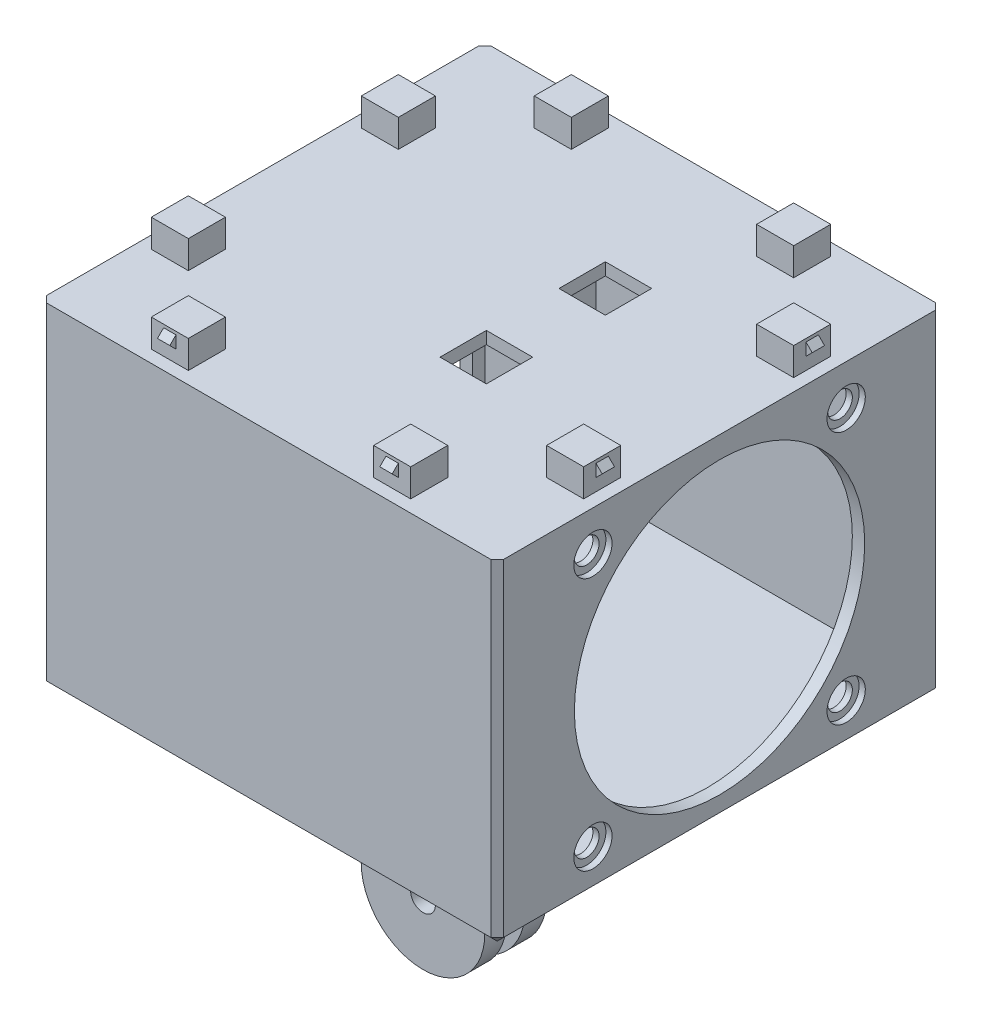
SolidWorks part; units mm, degrees
ref_plane "前视基准面" through (0, 0, 0) normal (0, 0, 1) x (1, 0, 0)
ref_plane "上视基准面" through (0, 0, 0) normal (0, 1, 0) x (1, 0, 0)
ref_plane "右视基准面" through (0, 0, 0) normal (1, 0, 0) x (0, 0, -1)
sketch "草图1" plane through (0, 0, 0) normal (0, 1, 0) x (1, 0, 0)
  line L1 (-65.7153, 32.1762) -> (8.2847, 32.1762)
  line L2 (-65.7153, 32.1762) -> (-65.7153, -39.8238)
  line L3 (-65.7153, -39.8238) -> (8.2847, -39.8238)
  line L4 (8.2847, 32.1762) -> (8.2847, -39.8238)
  dimension "D1" = 74
  dimension "D5" = 72
extrude "凸台-拉伸1" add sketch "草图1" along normal blind 54
sketch "草图2" plane through (0, 54, 0) normal (0, 1, 0) x (1, 0, 0)
  line L0 (8.2847, -39.8238) -> (8.2847, 32.1762) construction
  line L1 (6.2847, 30.1762) -> (-63.7153, 30.1762)
  line L2 (6.2847, 30.1762) -> (6.2847, -37.8238)
  line L3 (6.2847, -37.8238) -> (-63.7153, -37.8238)
  line L4 (-63.7153, 30.1762) -> (-63.7153, -37.8238)
  line L5 (-65.7153, -39.8238) -> (8.2847, -39.8238) construction
  line L6 (8.2847, 32.1762) -> (-65.7153, 32.1762) construction
  line L7 (-65.7153, 32.1762) -> (-65.7153, -39.8238) construction
  dimension "D1" = 2
  dimension "D2" = 2
  dimension "D3" = 2
  dimension "D4" = 2
extrude "切除-拉伸1" cut sketch "草图2" against normal blind 52
sketch "草图4" plane through (8.2847, 0, 0) normal (1, 0, 0) x (0, 0, -1)
  line L1 (32.1762, 54) -> (32.1762, 0) construction
  line L2 (-39.8238, 0) -> (32.1762, 0) construction
  circle A0 centre (-3.8238, 27) radius 23.5
  circle A1 centre (16.6762, 6.5) radius 2
  circle A2 centre (-24.3238, 47.5) radius 2
  circle A3 centre (-24.3238, 6.5) radius 2
  circle A4 centre (16.6762, 47.5) radius 2
  dimension "D1" = 47
  dimension "D2" = 20.5
  dimension "D8" = 4
  dimension "D3" = 20.5
  dimension "D4" = 20.5
  dimension "D5" = 20.5
  dimension "D6" = 36
  dimension "D7" = 27
extrude "切除-拉伸2" cut sketch "草图4" against normal blind 2
sketch "草图5" plane through (0, 0, 0) normal (0, -1, 0) x (1, 0, 0)
  line L0 (-65.7153, -32.1762) -> (-65.7153, 39.8238) construction
  line L1 (-63.7153, 37.8238) -> (-49.7153, 37.8238)
  line L2 (-63.7153, 37.8238) -> (-63.7153, -30.1762)
  line L3 (-63.7153, -30.1762) -> (-49.7153, -30.1762)
  line L4 (-49.7153, 37.8238) -> (-49.7153, -30.1762)
  line L5 (-65.7153, 39.8238) -> (8.2847, 39.8238) construction
  line L6 (8.2847, -32.1762) -> (-65.7153, -32.1762) construction
  dimension "D1" = 2
  dimension "D2" = 2
  dimension "D3" = 2
  dimension "D4" = 14
extrude "切除-拉伸3" cut sketch "草图5" against normal blind 2
sketch "草图6" plane through (0, 0, 37.8238) normal (0, 0, -1) x (-1, 0, 0)
  line L0 (63.7153, 54) -> (-6.2847, 54) construction
  line L1 (63.7153, 52) -> (54.7153, 52)
  line L2 (63.7153, 52) -> (63.7153, 54)
  line L3 (63.7153, 54) -> (54.7153, 54)
  line L4 (54.7153, 52) -> (54.7153, 54)
  line L9 (63.7153, 0) -> (63.7153, 54) construction
  dimension "D1" = 9
  dimension "D2" = 2
  dimension "D3" = 0
  dimension "D4" = 0
sketch "草图7" plane through (0, 0, -30.1762) normal (0, 0, 1) x (1, 0, 0)
  line L0 (-54.7153, 52) -> (-54.7153, 54) construction
  line L1 (-63.7153, 54) -> (-54.7153, 54)
  line L2 (-63.7153, 54) -> (-63.7153, 52)
  line L3 (-63.7153, 52) -> (-54.7153, 52)
  line L4 (-54.7153, 54) -> (-54.7153, 52)
  line L5 (-63.7153, 54) -> (-54.7153, 54) construction
  line L6 (6.2847, 54) -> (-63.7153, 54) construction
  line L7 (-63.7153, 0) -> (-63.7153, 54) construction
  point P12 (-63.7153, 53)
  dimension "D1" = 0
extrude "凸台-拉伸2" add sketch "草图6" along normal blind 5
extrude "凸台-拉伸3" add sketch "草图7" along normal blind 5
sketch "草图9" plane through (-65.7153, 0, 0) normal (-1, 0, 0) x (0, 0, 1)
  line L0 (39.8238, 54) -> (39.8238, 0) construction
  line L1 (35.8238, 50) -> (-28.1762, 50)
  line L2 (35.8238, 50) -> (35.8238, 4)
  line L3 (35.8238, 4) -> (-28.1762, 4)
  line L4 (-28.1762, 50) -> (-28.1762, 4)
  line L5 (-32.1762, 0) -> (39.8238, 0) construction
  line L6 (-32.1762, 54) -> (39.8238, 54) construction
  line L7 (-32.1762, 54) -> (-32.1762, 0) construction
  dimension "D1" = 4
  dimension "D2" = 4
  dimension "D3" = 4
  dimension "D4" = 4
extrude "切除-拉伸4" cut sketch "草图9" against normal up to next
sketch "草图10" plane through (0, 0, 37.8238) normal (0, 0, -1) x (-1, 0, 0)
  line L0 (49.7153, 2) -> (-6.2847, 2) construction
  line L9 (49.7153, 10) -> (45.7153, 10)
  line L10 (49.7153, 10) -> (49.7153, 18)
  line L11 (49.7153, 18) -> (45.7153, 18)
  line L12 (45.7153, 10) -> (45.7153, 18)
  line L13 (49.7153, 25) -> (49.7153, 33)
  line L14 (49.7153, 25) -> (45.7153, 25)
  line L15 (45.7153, 25) -> (45.7153, 33)
  line L16 (49.7153, 33) -> (45.7153, 33)
  line L17 (49.7153, 40) -> (49.7153, 48)
  line L18 (49.7153, 40) -> (45.7153, 40)
  line L19 (45.7153, 40) -> (45.7153, 48)
  line L20 (49.7153, 48) -> (45.7153, 48)
  line L21 (49.7153, 2) -> (49.7153, 0) construction
  point P0 (47.7153, 10)
  dimension "D1" = 4
  dimension "D2" = 8
  dimension "D3" = 8
  dimension "D4" = 3
extrude "凸台-拉伸5" add sketch "草图10" along normal blind 5
sketch "草图11" plane through (0, 0, -30.1762) normal (0, 0, 1) x (1, 0, 0)
  line L0 (6.2847, 2) -> (-49.7153, 2) construction
  line L1 (-45.7153, 10) -> (-49.7153, 10)
  line L2 (-45.7153, 10) -> (-45.7153, 18)
  line L3 (-45.7153, 18) -> (-49.7153, 18)
  line L4 (-49.7153, 10) -> (-49.7153, 18)
  line L5 (-45.7153, 25) -> (-45.7153, 33)
  line L6 (-45.7153, 25) -> (-49.7153, 25)
  line L7 (-49.7153, 25) -> (-49.7153, 33)
  line L8 (-45.7153, 33) -> (-49.7153, 33)
  line L9 (-45.7153, 40) -> (-45.7153, 48)
  line L10 (-45.7153, 40) -> (-49.7153, 40)
  line L11 (-49.7153, 40) -> (-49.7153, 48)
  line L12 (-45.7153, 48) -> (-49.7153, 48)
  line L13 (-49.7153, 2) -> (-49.7153, 0) construction
  dimension "D1" = 4
  dimension "D2" = 8
  dimension "D3" = 8
  dimension "D4" = 3
extrude "凸台-拉伸6" add sketch "草图11" along normal blind 5
sketch "草图15" plane through (0, 54, 0) normal (0, 1, 0) x (1, 0, 0)
  line L0 (6.2847, -37.8238) -> (6.2847, 30.1762) construction
  line L1 (-63.7153, 30.1762) -> (6.2847, 30.1762)
  line L2 (-63.7153, 30.1762) -> (-63.7153, -37.8238)
  line L3 (-63.7153, -37.8238) -> (6.2847, -37.8238)
  line L4 (6.2847, 30.1762) -> (6.2847, -37.8238)
  line L5 (-63.7153, 25.1762) -> (-63.7153, -32.8238) construction
extrude "凸台-拉伸7" add sketch "草图15" against normal blind 2
sketch "草图16" plane through (0, 54, 0) normal (0, 1, 0) x (1, 0, 0)
  line L0 (-43.7153, -31.8238) -> (-49.7153, -31.8238)
  line L1 (-57.7153, 16.1762) -> (-63.7153, 16.1762)
  line L2 (-57.7153, 16.1762) -> (-57.7153, 10.1762)
  line L3 (-57.7153, 10.1762) -> (-63.7153, 10.1762)
  line L4 (-63.7153, 16.1762) -> (-63.7153, 10.1762)
  line L5 (-43.7153, -31.8238) -> (-43.7153, -37.8238)
  line L6 (-43.7153, -37.8238) -> (-49.7153, -37.8238)
  line L7 (-49.7153, -31.8238) -> (-49.7153, -37.8238)
  line L8 (-7.7153, -31.8238) -> (-13.7153, -31.8238)
  line L9 (-7.7153, -31.8238) -> (-7.7153, -37.8238)
  line L10 (-7.7153, -37.8238) -> (-13.7153, -37.8238)
  line L11 (-13.7153, -31.8238) -> (-13.7153, -37.8238)
  line L12 (-43.7153, 30.1762) -> (-49.7153, 30.1762)
  line L13 (-43.7153, 30.1762) -> (-43.7153, 24.1762)
  line L14 (-43.7153, 24.1762) -> (-49.7153, 24.1762)
  line L15 (-49.7153, 30.1762) -> (-49.7153, 24.1762)
  line L16 (-7.7153, 30.1762) -> (-13.7153, 30.1762)
  line L17 (-7.7153, 30.1762) -> (-7.7153, 24.1762)
  line L18 (-7.7153, 24.1762) -> (-13.7153, 24.1762)
  line L19 (-13.7153, 30.1762) -> (-13.7153, 24.1762)
  line L20 (6.2847, 16.1762) -> (0.2847, 16.1762)
  line L21 (6.2847, 16.1762) -> (6.2847, 10.1762)
  line L22 (6.2847, 10.1762) -> (0.2847, 10.1762)
  line L23 (0.2847, 16.1762) -> (0.2847, 10.1762)
  line L24 (6.2847, -17.8238) -> (0.2847, -17.8238)
  line L25 (6.2847, -17.8238) -> (6.2847, -23.8238)
  line L26 (6.2847, -23.8238) -> (0.2847, -23.8238)
  line L27 (0.2847, -17.8238) -> (0.2847, -23.8238)
  line L32 (-57.7153, -17.8238) -> (-63.7153, -17.8238)
  line L33 (-57.7153, -17.8238) -> (-57.7153, -23.8238)
  line L34 (-57.7153, -23.8238) -> (-63.7153, -23.8238)
  line L35 (-63.7153, -17.8238) -> (-63.7153, -23.8238)
  line L36 (8.2847, 32.1762) -> (-65.7153, 32.1762) construction
  line L37 (-65.7153, -39.8238) -> (8.2847, -39.8238) construction
  line L38 (-65.7153, 32.1762) -> (-65.7153, -39.8238) construction
  line L39 (8.2847, -39.8238) -> (8.2847, 32.1762) construction
  point P42 (-10.7153, 30.1762)
  dimension "D1" = 16
  dimension "D2" = 16
  dimension "D3" = 16
  dimension "D4" = 16
  dimension "D5" = 16
  dimension "D6" = 16
  dimension "D7" = 16
  dimension "D8" = 16
  dimension "D9" = 6
  dimension "D10" = 2
  dimension "D11" = 2
  dimension "D12" = 2
  dimension "D13" = 2
extrude "凸台-拉伸8" add sketch "草图16" along normal blind 4.5
sketch "草图17" plane through (-63.7153, 0, 0) normal (-1, 0, 0) x (0, 0, 1)
  line L1 (-14.1762, 58) -> (-12.1762, 58)
  line L2 (-14.1762, 58) -> (-14.1762, 56)
  line L3 (-14.1762, 56) -> (-12.1762, 56)
  line L4 (-12.1762, 58) -> (-12.1762, 56)
  line L5 (19.8238, 58) -> (21.8238, 58)
  line L6 (19.8238, 58) -> (19.8238, 56)
  line L7 (19.8238, 56) -> (21.8238, 56)
  line L8 (21.8238, 58) -> (21.8238, 56)
  line L9 (17.8238, 54) -> (23.8238, 54) construction
  line L10 (23.8238, 58.5) -> (23.8238, 54) construction
  line L11 (-10.1762, 58.5) -> (-10.1762, 54) construction
  dimension "D1" = 2
  dimension "D2" = 2
  dimension "D3" = 2
  dimension "D4" = 2
extrude "凸台-拉伸9" add sketch "草图17" along normal blind 1
sketch "草图18" plane through (0, 0, 37.8238) normal (0, 0, 1) x (1, 0, 0)
  line L0 (-13.7153, 54) -> (-7.7153, 54) construction
  line L1 (-9.7153, 56) -> (-11.7153, 56)
  line L2 (-9.7153, 56) -> (-9.7153, 58)
  line L3 (-9.7153, 58) -> (-11.7153, 58)
  line L4 (-11.7153, 56) -> (-11.7153, 58)
  line L5 (-45.7153, 56) -> (-47.7153, 56)
  line L6 (-45.7153, 56) -> (-45.7153, 58)
  line L7 (-45.7153, 58) -> (-47.7153, 58)
  line L8 (-47.7153, 56) -> (-47.7153, 58)
  line L9 (-7.7153, 58.5) -> (-7.7153, 54) construction
  line L10 (-43.7153, 58.5) -> (-43.7153, 54) construction
  point P11 (-9.7153, 57)
  dimension "D1" = 2
  dimension "D2" = 2
  dimension "D3" = 2
  dimension "D4" = 2
extrude "凸台-拉伸10" add sketch "草图18" along normal blind 1
sketch "草图19" plane through (6.2847, 0, 0) normal (1, 0, 0) x (0, 0, -1)
  line L0 (10.1762, 54) -> (16.1762, 54) construction
  line L1 (14.1762, 56) -> (12.1762, 56)
  line L2 (14.1762, 56) -> (14.1762, 58)
  line L3 (14.1762, 58) -> (12.1762, 58)
  line L4 (12.1762, 56) -> (12.1762, 58)
  line L5 (-19.8238, 56) -> (-21.8238, 56)
  line L6 (-19.8238, 56) -> (-19.8238, 58)
  line L7 (-19.8238, 58) -> (-21.8238, 58)
  line L8 (-21.8238, 56) -> (-21.8238, 58)
  line L9 (16.1762, 58.5) -> (16.1762, 54) construction
  line L10 (-17.8238, 58.5) -> (-17.8238, 54) construction
  dimension "D1" = 2
  dimension "D2" = 2
  dimension "D3" = 2
  dimension "D4" = 2
extrude "凸台-拉伸11" add sketch "草图19" along normal blind 1
sketch "草图20" plane through (0, 0, -30.1762) normal (0, 0, -1) x (-1, 0, 0)
  line L1 (47.7153, 56) -> (45.7153, 56)
  line L2 (47.7153, 56) -> (47.7153, 58)
  line L3 (47.7153, 58) -> (45.7153, 58)
  line L4 (45.7153, 56) -> (45.7153, 58)
  line L5 (11.7153, 56) -> (9.7153, 56)
  line L6 (11.7153, 56) -> (11.7153, 58)
  line L7 (11.7153, 58) -> (9.7153, 58)
  line L8 (9.7153, 56) -> (9.7153, 58)
  line L9 (43.7153, 54) -> (49.7153, 54) construction
  line L10 (49.7153, 58.5) -> (49.7153, 54) construction
  line L11 (13.7153, 58.5) -> (13.7153, 54) construction
  dimension "D1" = 2
  dimension "D2" = 2
  dimension "D3" = 2
  dimension "D4" = 2
extrude "凸台-拉伸12" add sketch "草图20" along normal blind 1
sketch "草图21" plane through (0, 52, 0) normal (0, -1, 0) x (-1, 0, 0)
  line L0 (-6.2847, -37.8238) -> (-6.2847, 30.1762) construction
  line L1 (17.7153, -15.5749) -> (25.2153, -15.5749)
  line L2 (17.7153, -15.5749) -> (17.7153, -8.0749)
  line L3 (17.7153, -8.0749) -> (25.2153, -8.0749)
  line L4 (25.2153, -15.5749) -> (25.2153, -8.0749)
  line L5 (17.7153, 3.6832) -> (25.2153, 3.6832)
  line L6 (17.7153, 3.6832) -> (17.7153, 11.1832)
  line L7 (17.7153, 11.1832) -> (25.2153, 11.1832)
  line L8 (25.2153, 3.6832) -> (25.2153, 11.1832)
  dimension "D1" = 7.5
  dimension "D2" = 24
extrude "切除-拉伸5" cut sketch "草图21" against normal up to next
sketch "草图25" plane through (0, 0, 0) normal (0, -1, 0) x (1, 0, 0)
  line L0 (8.2847, 39.8238) -> (8.2847, -32.1762) construction
  line L1 (-24.7278, 8.8238) -> (-44.7278, 8.8238)
  line L2 (-24.7278, 8.8238) -> (-24.7278, -1.1762)
  line L3 (-24.7278, -1.1762) -> (-44.7278, -1.1762)
  line L4 (-44.7278, 8.8238) -> (-44.7278, -1.1762)
  point P6 (8.2847, 3.8238)
  point P7 (-24.7278, 3.8238)
  dimension "D1" = 20
  dimension "D2" = 10
extrude "凸台-拉伸15" add sketch "草图25" along normal blind 30
sketch "草图26" plane through (0, 0, 8.8238) normal (0, 0, 1) x (1, 0, 0)
  line L0 (-24.7278, -30) -> (-44.7278, -30) construction
  circle A0 centre (-34.7278, -30) radius 10
extrude "凸台-拉伸16" add sketch "草图26" against normal blind 10
sketch "草图27" plane through (0, 0, 8.8238) normal (0, 0, 1) x (1, 0, 0)
  circle A0 centre (-34.7278, -30) radius 2
  arc A1 (-44.7278, -30) -> (-24.7278, -30) centre (-34.7278, -30) ccw construction
  dimension "D1" = 4
extrude "切除-拉伸6" cut sketch "草图27" against normal blind 10
sketch "草图29" plane through (-44.7278, 0, 0) normal (-1, 0, 0) x (0, 0, 1)
  line L1 (5.3238, -40) -> (2.3238, -40)
  line L2 (5.3238, -40) -> (5.3238, -13)
  line L3 (5.3238, -13) -> (2.3238, -13)
  line L4 (2.3238, -40) -> (2.3238, -13)
  line L5 (8.8238, 0) -> (-1.1762, 0) construction
  point P7 (3.8238, 0)
  point P8 (3.8238, -13)
  dimension "D1" = 3
  dimension "D2" = 27
extrude "切除-拉伸7" cut sketch "草图29" against normal up to next
sketch "草图30" plane through (0, -13, 0) normal (0, -1, 0) x (1, 0, 0)
  line L0 (-24.7278, 5.3238) -> (-44.7278, 5.3238) construction
  line L1 (-33.2278, 2.3238) -> (-36.2278, 2.3238)
  line L2 (-33.2278, 2.3238) -> (-33.2278, 5.3238)
  line L3 (-33.2278, 5.3238) -> (-36.2278, 5.3238)
  line L4 (-36.2278, 2.3238) -> (-36.2278, 5.3238)
  line L5 (-24.7278, 2.3238) -> (-44.7278, 2.3238) construction
  point P8 (-34.7278, 2.3238)
  point P9 (-34.7278, 2.3238)
  dimension "D1" = 3
extrude "切除-拉伸8" cut sketch "草图30" against normal up to next
chamfer "倒角1" distance 1 angle 45 8 edges at (-65.7153, 27, 39.8238) (8.2847, 27, 39.8238) (8.2847, 27, -32.1762) (-65.7153, 27, -32.1762) (-28.7153, 0, 39.8238) (-65.7153, 0, 3.8238) (-28.7153, 0, -32.1762) (8.2847, 0, 3.8238)
chamfer "倒角2" distance 1 angle 45 8 edges at (7.2847, 58, 20.8238) (7.2847, 58, -13.1762) (-10.7153, 58, -31.1762) (-46.7153, 58, -31.1762) (-64.7153, 58, -13.1762) (-64.7153, 58, 20.8238) (-10.7153, 58, 38.8238) (-46.7153, 58, 38.8238)
sketch "草图31" plane through (8.2847, 0, 0) normal (1, 0, 0) x (0, 0, -1)
  circle A0 centre (16.6762, 6.5) radius 3.1
  circle A1 centre (-24.3238, 6.5) radius 3.1
  circle A2 centre (-24.3238, 47.5) radius 3.1
  circle A3 centre (16.6762, 47.5) radius 3.1
  circle A4 centre (16.6762, 6.5) radius 2 construction
  circle A5 centre (-24.3238, 6.5) radius 2 construction
  circle A6 centre (-24.3238, 47.5) radius 2 construction
  circle A7 centre (16.6762, 47.5) radius 2 construction
  dimension "D1" = 6.2
extrude "切除-拉伸9" cut sketch "草图31" against normal blind 1
chamfer "倒角3" distance 1 angle 45 8 edges at (-64.7153, 56, 20.8238) (-64.7153, 56, -13.1762) (-46.7153, 56, -31.1762) (-10.7153, 56, -31.1762) (7.2847, 56, -13.1762) (7.2847, 56, 20.8238) (-46.7153, 56, 38.8238) (-10.7153, 56, 38.8238)
